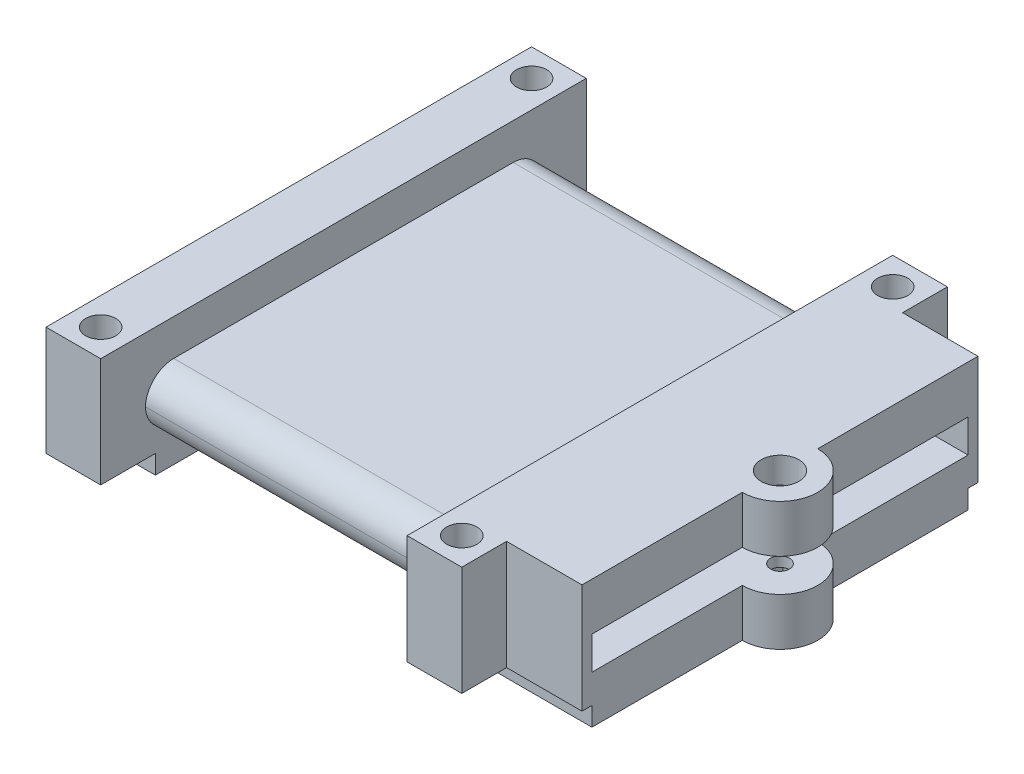
SolidWorks part; units mm, degrees
ref_plane "Front Plane" through (0, 0, 0) normal (0, 0, 1) x (1, 0, 0)
ref_plane "Top Plane" through (0, 0, 0) normal (0, 1, 0) x (1, 0, 0)
ref_plane "Right Plane" through (0, 0, 0) normal (1, 0, 0) x (0, 0, -1)
sketch "Sketch1" plane through (0, 0, 0) normal (1, 0, 0) x (0, 0, -1)
  line L0 (21, 5.9) -> (21, 0) construction
  line L1 (0, 0) -> (42, 0)
  line L2 (0, 0) -> (0, 5.9)
  line L3 (0, 5.9) -> (42, 5.9)
  line L4 (42, 0) -> (42, 5.9)
  line L6 (1.05, 1.2) -> (40.95, 1.2)
  line L7 (1.05, 1.2) -> (1.05, 4.7)
  line L8 (1.05, 4.7) -> (40.95, 4.7)
  line L9 (40.95, 1.2) -> (40.95, 4.7)
  line L10 (1.05, 1.2) -> (40.95, 4.7) construction
  line L11 (1.05, 4.7) -> (40.95, 1.2) construction
  point P7 (21, 2.95)
  dimension "D1" = 42
  dimension "D2" = 5.9
  dimension "D3" = 3.5
  dimension "D4" = 39.9
extrude "Boss-Extrude1" add sketch "Sketch1" along normal blind 32.5
fillet "Fillet2" radius 3 4 edges at (16.25, 0, -42) (16.25, 0, 0) (16.25, 5.9, 0) (16.25, 5.9, -42)
sketch "Sketch2" plane through (32.5, 0, 0) normal (1, 0, 0) x (0, 0, -1)
  line L0 (21, 5.9) -> (21, 0) construction
  line L1 (39, 5.9) -> (3, 5.9) construction
  line L2 (3, 0) -> (39, 0) construction
  line L4 (-4.75, -3.85) -> (46.75, -3.85)
  line L5 (-4.75, -3.85) -> (-4.75, 9.75)
  line L6 (-4.75, 9.75) -> (46.75, 9.75)
  line L7 (46.75, -3.85) -> (46.75, 9.75)
  line L8 (-4.75, -3.85) -> (46.75, 9.75) construction
  line L9 (-4.75, 9.75) -> (46.75, -3.85) construction
  line L14 (40.95, 1.2) -> (1.05, 1.2)
  line L15 (40.95, 1.2) -> (40.95, 4.7)
  line L16 (40.95, 4.7) -> (1.05, 4.7)
  line L17 (1.05, 1.2) -> (1.05, 4.7)
  line L18 (40.95, 1.2) -> (1.05, 4.7) construction
  line L19 (40.95, 4.7) -> (1.05, 1.2) construction
  point P6 (21, 2.95)
  point P11 (21, 2.95)
  point P12 (21, 2.95)
  dimension "D1" = 13.6
  dimension "D2" = 51.5
extrude "Boss-Extrude2" add sketch "Sketch2" along normal blind 5.8
sketch "Sketch3" plane through (0, 0, 0) normal (-1, 0, 0) x (0, 0, 1)
  line L0 (-21, 5.9) -> (-21, 0) construction
  line L1 (-39, 5.9) -> (-3, 5.9) construction
  line L2 (-3, 0) -> (-39, 0) construction
  line L4 (4.75, -3.85) -> (-46.75, -3.85)
  line L5 (4.75, -3.85) -> (4.75, 9.75)
  line L6 (4.75, 9.75) -> (-46.75, 9.75)
  line L7 (-46.75, -3.85) -> (-46.75, 9.75)
  line L8 (4.75, -3.85) -> (-46.75, 9.75) construction
  line L9 (4.75, 9.75) -> (-46.75, -3.85) construction
  line L10 (-1.05, 1.2) -> (-40.95, 1.2)
  line L11 (-1.05, 1.2) -> (-1.05, 4.7)
  line L12 (-1.05, 4.7) -> (-40.95, 4.7)
  line L13 (-40.95, 1.2) -> (-40.95, 4.7)
  line L14 (-1.05, 1.2) -> (-40.95, 4.7) construction
  line L15 (-1.05, 4.7) -> (-40.95, 1.2) construction
  point P6 (-21, 2.95)
  point P12 (-21, 2.95)
extrude "Boss-Extrude3" add sketch "Sketch3" along normal blind 5.8
sketch "Sketch4" plane through (0, 9.75, 0) normal (0, 1, 0) x (1, 0, 0)
  line L0 (-2.9, 46.75) -> (-2.9, 43.85) construction
  line L1 (-5.8, 46.75) -> (0, 46.75) construction
  line L2 (35.4, 46.75) -> (35.4, 43.85) construction
  line L3 (38.3, 46.75) -> (32.5, 46.75) construction
  line L4 (-2.9, -4.75) -> (-2.9, -1.85) construction
  line L5 (-5.8, -4.75) -> (0, -4.75) construction
  line L6 (35.4, -4.75) -> (35.4, -1.85) construction
  line L7 (38.3, -4.75) -> (32.5, -4.75) construction
  circle A0 centre (-2.9, 43.85) radius 1.6
  circle A1 centre (35.4, 43.85) radius 1.6
  circle A2 centre (-2.9, -1.85) radius 1.6
  circle A3 centre (35.4, -1.85) radius 1.6
  dimension "D2" = 3.2
  dimension "D4" = 3.2
  dimension "D6" = 3.2
  dimension "D8" = 3.2
  dimension "D1" = 2.9
  dimension "D3" = 2.9
  dimension "D5" = 2.9
  dimension "D7" = 2.9
extrude "Cut-Extrude1" cut sketch "Sketch4" against normal through all
sketch "Sketch6" plane through (38.3, 0, 0) normal (1, 0, 0) x (0, 0, -1)
  line L0 (46.75, -3.85) -> (46.75, 9.75) construction
  line L1 (-4.75, -3.85) -> (46.75, -3.85)
  line L2 (-4.75, -3.85) -> (-4.75, 3.35)
  line L3 (-4.75, 3.35) -> (46.75, 3.35)
  line L4 (46.75, -3.85) -> (46.75, 3.35)
  dimension "D1" = 7.2
extrude "Cut-Extrude2" [suppressed] cut sketch "Sketch6" against normal blind 5.8
sketch "Sketch7" plane through (-5.8, 0, 0) normal (-1, 0, 0) x (0, 0, 1)
  line L0 (4.75, -3.85) -> (4.75, 9.75) construction
  line L1 (-46.75, -3.85) -> (4.75, -3.85)
  line L2 (-46.75, -3.85) -> (-46.75, 3.35)
  line L3 (-46.75, 3.35) -> (4.75, 3.35)
  line L4 (4.75, -3.85) -> (4.75, 3.35)
  dimension "D1" = 7.2
extrude "Cut-Extrude3" [suppressed] cut sketch "Sketch7" against normal blind 5.8
sketch "Sketch8" plane through (0, 9.75, 0) normal (0, 1, 0) x (1, 0, 0)
  line L1 (0, 41.9996) -> (32.5, 41.9996) construction
  line L2 (38.3, 46.75) -> (38.3, -4.75) construction
  line L3 (46.3, 25) -> (46.3, 41.9996)
  line L4 (46.3, 41.9996) -> (38.3, 41.9996)
  line L5 (46.3, 17) -> (46.3, 0.0004)
  line L6 (46.3, 0.0004) -> (38.3, 0.0004)
  line L12 (-42.1211, 21) -> (79.5205, 21) construction
  line L13 (-5.8, -4.75) -> (-5.8, 46.75) construction
  circle A0 centre (46.3, 21) radius 4
  point P3 (79.5205, 21)
  point P14 (-42.1211, 48.2101)
  point P17 (-5.8, 21)
  point P18 (0, 0)
  point P19 (-8.5524, 21)
  point P20 (0, 0)
  point P21 (0, 0)
  line M5 (38.3, -4.75) -> (38.3, 46.75)
  dimension "D1" = 8
  dimension "D2" = 8
extrude "Boss-Extrude4" add sketch "Sketch8" against normal blind 13.6 contours A0 L3 L4 M5 | A0 L6 L5 M5 | A0 | A0 L12 region at (42.1139, 9.75, -32.2114) region at (46.3, 9.75, -22.6977) region at (46.3, 9.75, -19.3023) region at (42.1139, 9.75, -9.7886)
hole_wizard "CSK for M2 Flat Head Machine Screw1" positions "Sketch12" profile "Sketch13" countersink size "M2" standard "ANSI Metric" end condition through all
sketch "Sketch12" plane through (0, 9.75, 0) normal (0, 1, 0) x (1, 0, 0)
  point P0 (46.3, 21)
sketch "Sketch13" plane through (46.3, 9.75, -21) normal (1, 0, 0) x (0, 0, 1)
  line L0 (0, 0) -> (0, 13.6)
  line L1 (0, 13.6) -> (1, 13.6)
  line L2 (1, 13.6) -> (1, 3.75)
  line L3 (1, 3.75) -> (2, 2.75)
  line L4 (2, 2.75) -> (2, 0)
  line L6 (2, 0) -> (0, 0)
  line L7 (-1, 3.75) -> (-2, 2.75) construction
  line L11 (0, -6.35) -> (0, 107.95) construction
  dimension "Thru Hole Dia." = 2
  dimension "Thru Hole Depth" = 13.6
  dimension "C'Sink Dia." = 4
  dimension "C'Sink Angle" = 90
  dimension "Head Clearance" = 2.75
sketch "Sketch14" plane through (0, -3.85, 0) normal (0, -1, 0) x (1, 0, 0)
  line L1 (43.9126, -20.5753) -> (44.7385, -22.8552)
  line L2 (44.7385, -22.8552) -> (47.1259, -23.2799)
  line L3 (47.1259, -23.2799) -> (48.6874, -21.4247)
  line L4 (48.6874, -21.4247) -> (47.8615, -19.1448)
  line L5 (47.8615, -19.1448) -> (45.4741, -18.7201)
  line L6 (45.4741, -18.7201) -> (43.9126, -20.5753)
  circle A0 centre (46.3, -21) radius 2.1 construction
  dimension "D1" = 4.2
extrude "Cut-Extrude4" cut sketch "Sketch14" against normal blind 4
sketch "Sketch15" plane through (-5.8, 0, 0) normal (-1, 0, 0) x (0, 0, 1)
  line L1 (-40.95, 1.2) -> (-1.05, 1.2)
  line L2 (-40.95, 1.2) -> (-40.95, 4.7)
  line L3 (-40.95, 4.7) -> (-1.05, 4.7)
  line L4 (-1.05, 1.2) -> (-1.05, 4.7)
  line L5 (-46.75, -3.85) -> (-40.95, -3.85)
  line L6 (-46.75, -3.85) -> (-46.75, -1.85)
  line L7 (-46.75, -1.85) -> (-40.95, -1.85)
  line L8 (-40.95, -3.85) -> (-40.95, -1.85)
  line L9 (4.75, -3.85) -> (-1.05, -3.85)
  line L10 (4.75, -3.85) -> (4.75, -1.85)
  line L11 (4.75, -1.85) -> (-1.05, -1.85)
  line L12 (-1.05, -3.85) -> (-1.05, -1.85)
  dimension "D1" = 5.8
  dimension "D2" = 2
  dimension "D3" = 5.8
  dimension "D4" = 2
extrude "Cut-Extrude5" cut sketch "Sketch15" against normal through all
